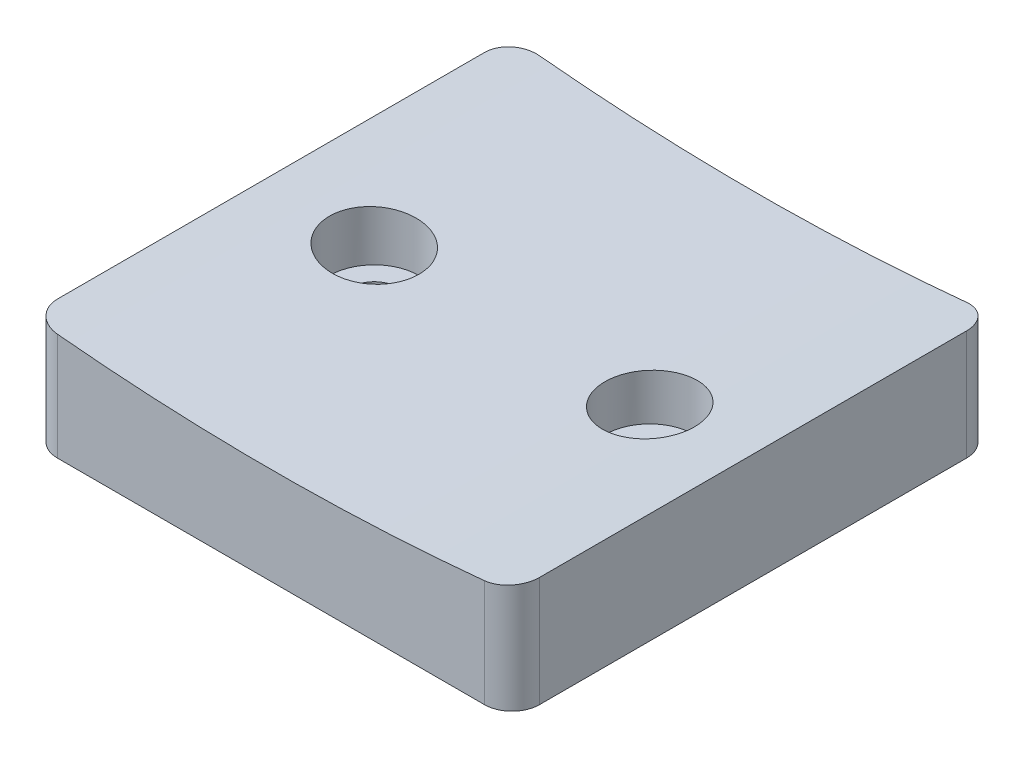
SolidWorks part; units mm, degrees
ref_plane "Спереди" through (0, 0, 0) normal (0, 0, 1) x (1, 0, 0)
ref_plane "Сверху" through (0, 0, 0) normal (0, 1, 0) x (1, 0, 0)
ref_plane "Справа" through (0, 0, 0) normal (1, 0, 0) x (0, 0, -1)
sketch "Эскиз2" plane through (0, 0, 0) normal (0, 1, 0) x (-1, 0, 0)
  line L0 (5, -17.5) -> (-5, -17.5)
  line L1 (-5, 17.5) -> (5, 17.5)
  line L8 (-17.5, 15.5) -> (-17.5, -15.5)
  line L9 (-15.5, -17.5) -> (-5, -17.5)
  line L11 (-5, 17.5) -> (-15.5, 17.5)
  line L16 (5, -17.5) -> (15.5, -17.5)
  line L17 (17.5, -15.5) -> (17.5, 15.5)
  line L18 (15.5, 17.5) -> (5, 17.5)
  line L34 (11.5, -7) -> (11.5, -13)
  line L35 (8.5, -13) -> (11.5, -13)
  line L36 (8.5, -7) -> (8.5, -13)
  line L37 (8.5, -7) -> (11.5, -7)
  line L38 (8.5, 7) -> (11.5, 7)
  line L39 (11.5, 13) -> (11.5, 7)
  line L40 (8.5, 13) -> (11.5, 13)
  line L41 (8.5, 13) -> (8.5, 7)
  line L42 (-11.5, 7) -> (-8.5, 7)
  line L43 (-8.5, 13) -> (-8.5, 7)
  line L44 (-11.5, 13) -> (-8.5, 13)
  line L45 (-11.5, 13) -> (-11.5, 7)
  line L46 (-11.5, -13) -> (-8.5, -13)
  line L47 (-8.5, -7) -> (-8.5, -13)
  line L48 (-11.5, -7) -> (-8.5, -7)
  line L49 (-11.5, -7) -> (-11.5, -13)
  arc A4 (-17.5, -15.5) -> (-15.5, -17.5) centre (-15.5, -15.5) ccw
  arc A5 (-15.5, 17.5) -> (-17.5, 15.5) centre (-15.5, 15.5) ccw
  arc A8 (15.5, -17.5) -> (17.5, -15.5) centre (15.5, -15.5) ccw
  arc A9 (17.5, 15.5) -> (15.5, 17.5) centre (15.5, 15.5) ccw
  circle A10 centre (10, 0) radius 1.75
  circle A11 centre (-10, 0) radius 1.75
extrude "Бобышка-Вытянуть1" add sketch "Эскиз2" along normal blind 8 contours L1 L18 A9 L17 A8 L16 L0 L9 A4 L8 A5 L11 | A10 | A11
sketch "Эскиз4" plane through (0, 0, 17.5) normal (0, 0, 1) x (1, 0, 0)
  arc A0 (-17.5, 8) -> (17.5, 8) centre (0, 167.0401) ccw
  dimension "D1" = 160
extrude "Вырез-Вытянуть1" cut sketch "Эскиз4" against normal through all and the other way through all
sketch "Эскиз5" plane through (0, 0, -17.5) normal (0, 0, -1) x (-1, 0, 0)
  line L0 (-10.0006, 7.3529) -> (10.0006, 7.3529) construction
  arc A0 (-11.75, 7.4721) -> (-8.25, 7.2529) centre (0, 167.0401) ccw construction
  arc A1 (-11.75, 7.4721) -> (-8.25, 7.2529) centre (0, 167.0401) ccw
  arc A2 (8.25, 7.2529) -> (11.75, 7.4721) centre (0, 167.0401) ccw construction
  arc A3 (8.25, 7.2529) -> (11.75, 7.4721) centre (0, 167.0401) ccw
ref_plane "Плоскость1" through (0, 7.3529, 0) normal (0, -1, 0) x (-1, 0, 0)
sketch "Эскиз6" plane through (0, 7.3529, 0) normal (0, -1, 0) x (-1, 0, 0)
  circle A0 centre (10, 0) radius 3.25
  circle A1 centre (-10, 0) radius 3.25
  dimension "D1" = 6.5
  dimension "D2" = 6.5
extrude "Вырез-Вытянуть2" cut sketch "Эскиз6" along normal blind 3.5 and the other way blind 3.5
